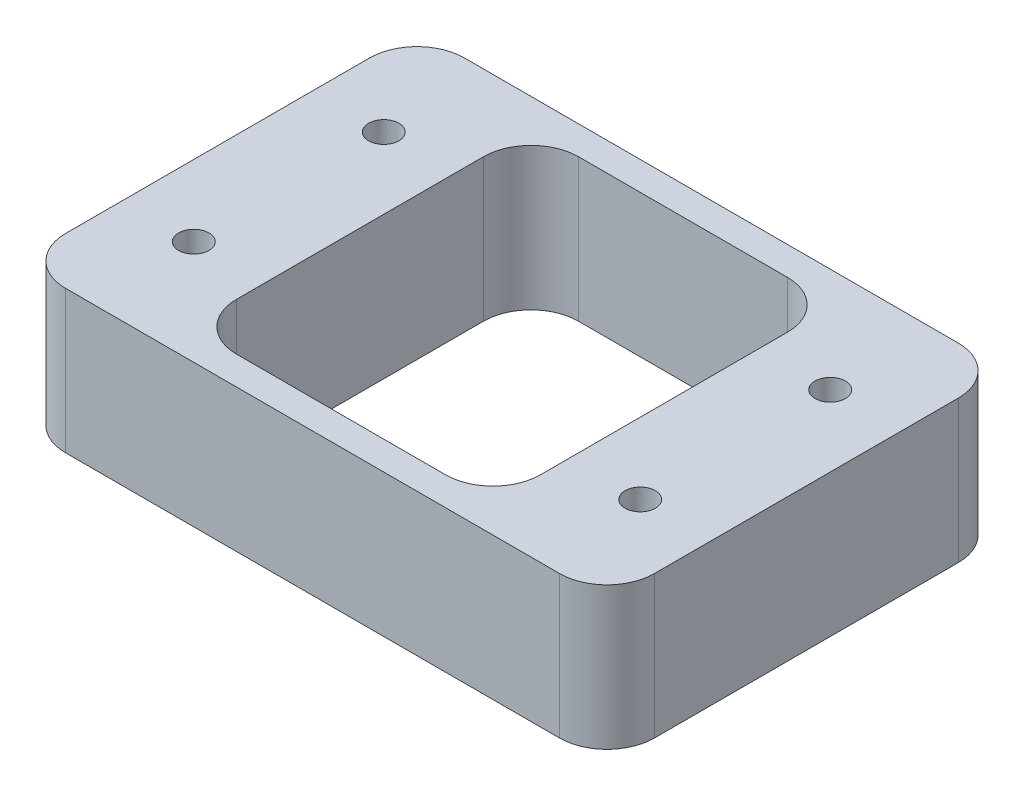
SolidWorks part; units mm, degrees
material "ABS"
ref_plane "Front Plane" through (0, 0, 0) normal (0, 0, 1) x (1, 0, 0)
ref_plane "Top Plane" through (0, 0, 0) normal (0, 1, 0) x (1, 0, 0)
ref_plane "Right Plane" through (0, 0, 0) normal (1, 0, 0) x (0, 0, -1)
sketch "Sketch1" plane through (0, 0, 0) normal (0, 1, 0) x (1, 0, 0)
  line L0 (7.5, 42) -> (7.5, 0) construction
  line L1 (0, 0) -> (62, 0)
  line L2 (0, 0) -> (0, 42)
  line L3 (0, 42) -> (62, 42)
  line L4 (62, 0) -> (62, 42)
  line L5 (31, 42) -> (31, 0) construction
  line L6 (62, 21) -> (0, 21) construction
  circle A0 centre (7.5, 31) radius 1.6
  circle A1 centre (7.5, 11) radius 1.6
  circle A2 centre (54.5, 11) radius 1.6
  circle A3 centre (54.5, 31) radius 1.6
  dimension "D3" = 20
  dimension "D4" = 3.2
  dimension "D1" = 62
  dimension "D2" = 42
  dimension "D5" = 7.5
extrude "Boss-Extrude1" add sketch "Sketch1" along normal blind 15
sketch "Sketch2" plane through (0, 15, 0) normal (0, 1, 0) x (1, 0, 0)
  line L0 (62, 42) -> (0, 42) construction
  line L5 (0, 21) -> (62, 21) construction
  line L6 (0, 42) -> (0, 0) construction
  line L7 (62, 0) -> (62, 42) construction
  line L8 (15, 3) -> (47, 3)
  line L9 (15, 3) -> (15, 39)
  line L10 (15, 39) -> (47, 39)
  line L11 (47, 3) -> (47, 39)
  line L12 (15, 3) -> (47, 39) construction
  line L13 (15, 39) -> (47, 3) construction
  point P0 (31, 21)
  dimension "D1" = 3
  dimension "D2" = 15
extrude "Cut-Extrude1" cut sketch "Sketch2" against normal through all
fillet "Fillet1" radius 5 8 edges at (0, 7.5, -42) (62, 7.5, -42) (62, 7.5, 0) (0, 7.5, 0) (47, 7.5, -3) (15, 7.5, -39) (47, 7.5, -39) (15, 7.5, -3)
